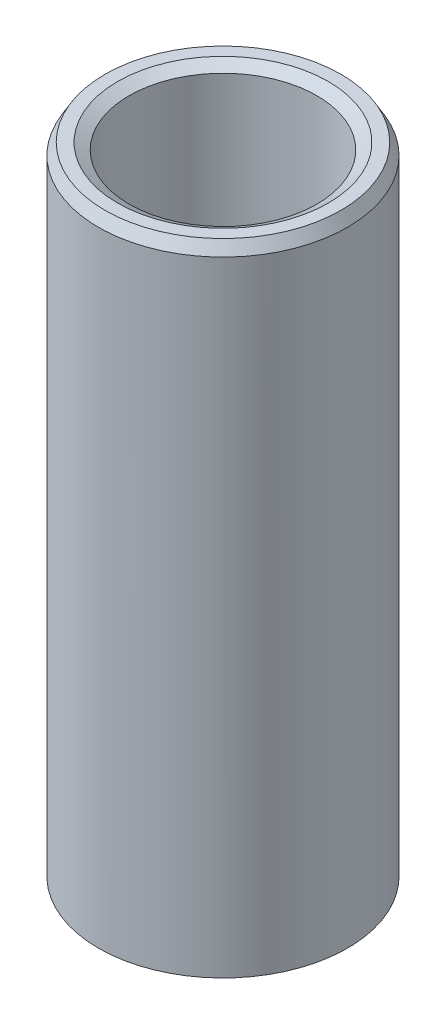
SolidWorks part; units mm, degrees
ref_plane "Front Plane" through (0, 0, 0) normal (0, 0, 1) x (1, 0, 0)
ref_plane "Top Plane" through (0, 0, 0) normal (0, 1, 0) x (1, 0, 0)
ref_plane "Right Plane" through (0, 0, 0) normal (1, 0, 0) x (0, 0, -1)
sketch "Sketch1" plane through (0, 0, 0) normal (0, 1, 0) x (1, 0, 0)
  circle A0 centre (0, 0) radius 42.5
  dimension "SLEEVE_OD" = 85
extrude "Boss-Extrude1" add sketch "Sketch1" along normal blind 219.2366
sketch "Sketch2" plane through (0, 0, 0) normal (0, 1, 0) x (1, 0, 0)
  circle A0 centre (0, 0) radius 32.0603
  dimension "BORE_D" = 64.1206
extrude "Cut-Extrude1" cut sketch "Sketch2" along normal through all
chamfer "Chamfer1" distance 3.8927 angle 30 4 edges at (0, 219.2366, 32.0603) (0, 0, 32.0603) (0, 0, 42.5) (0, 219.2366, 42.5) first distance on face at (0, 219.2366, 32.0603) first distance on face at (0, 0, 32.0603) first distance on face at (0, 219.2366, 42.5)
